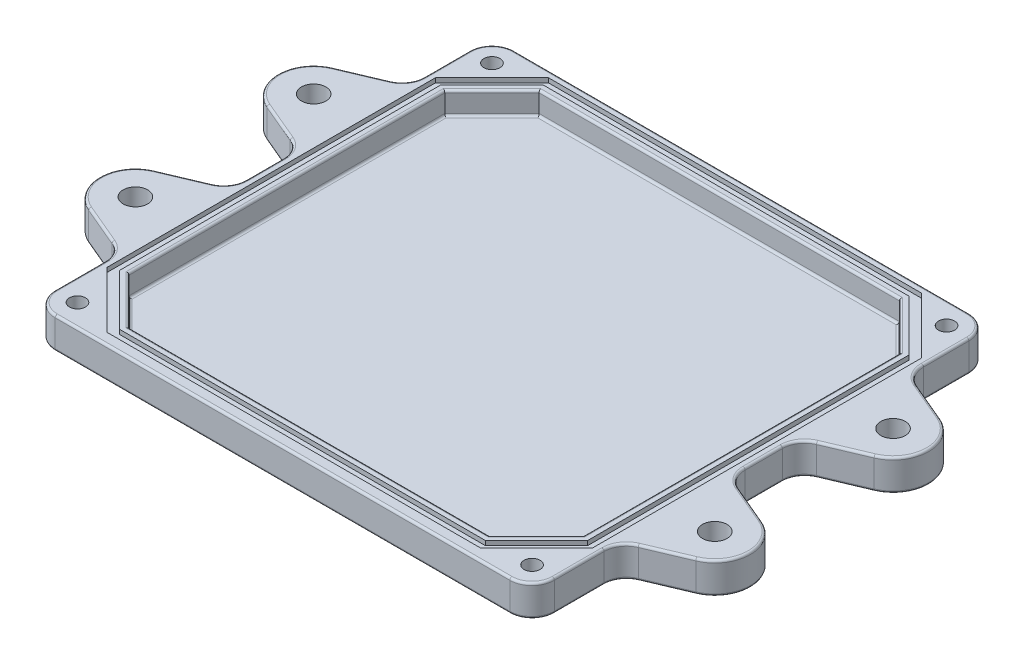
SolidWorks part; units mm, degrees
material "ABS"
ref_plane "Front Plane" through (0, 0, 0) normal (0, 0, 1) x (1, 0, 0)
ref_plane "Top Plane" through (0, 0, 0) normal (0, 1, 0) x (1, 0, 0)
ref_plane "Right Plane" through (0, 0, 0) normal (1, 0, 0) x (0, 0, -1)
ref_plane "PCB Top Plane" through (0, 10, 0) normal (0, 1, 0) x (1, 0, 0)
sketch "PCB Sketch" plane through (0, 10, 0) normal (0, 1, 0) x (1, 0, 0)
  line L0 (-50, 35) -> (-50, -35) construction
  line L1 (-50, -35) -> (-40, -45) construction
  line L2 (-40, -45) -> (40, -45) construction
  line L3 (40, -45) -> (50, -35) construction
  line L4 (50, -35) -> (50, 35) construction
  line L5 (50, 35) -> (40, 45) construction
  line L6 (40, 45) -> (-40, 45) construction
  line L7 (-40, 45) -> (-50, 35) construction
  line L8 (-29.625, -49.5) -> (29.625, -49.5) construction
  point P4 (-40, 35)
  point P9 (40, 35)
  point P10 (40, -35)
  point P11 (-40, -35)
  point P12 (0, 12)
  point P13 (0, 45)
  point P15 (50, 0)
  point P16 (0, -40)
  point P19 (0, -49.5)
  dimension "D1" = 100
  dimension "D2" = 90
  dimension "D3" = 10
  dimension "D4" = 57
  dimension "D5" = 5
  dimension "D6" = 59.25
  dimension "D7" = 9.5
ref_plane "Connector Front Plane" through (0, 0, 49.5) normal (0, 0, 1) x (1, 0, 0)
sketch "Connector Front Sketch" plane through (0, 0, 49.5) normal (0, 0, 1) x (1, 0, 0)
  line L0 (-29.605, 45.26) -> (29.605, 45.26) construction
  line L1 (29.605, 45.26) -> (29.605, 10) construction
  line L2 (29.605, 10) -> (-29.605, 10) construction
  line L3 (-29.605, 10) -> (-29.605, 45.26) construction
  line L4 (-29.625, 10) -> (29.625, 10) construction
  line L5 (-24.65, 27.63) -> (24.65, 27.63) construction
  point P6 (0, 45.26)
  point P11 (0, 27.63)
  point P12 (29.605, 27.63)
  point P14 (-24.65, 27.63)
  point P15 (24.65, 27.63)
  dimension "D1" = 35.26
  dimension "D2" = 59.21
  dimension "D3" = 49.3
sketch "Connector Right Sketch" plane through (0, 0, 0) normal (1, 0, 0) x (0, 0, -1)
  line L0 (-49.5, 10) -> (-49.5, 45.26) construction
  line L1 (-49.5, 10) -> (-49.5, 45.26) construction
  line L2 (-49.5, 45.26) -> (-34.01, 45.26) construction
  line L3 (-34.01, 45.26) -> (-34.01, 10) construction
  line L4 (-34.01, 10) -> (-49.5, 10) construction
  line L5 (-49.5, 38.755) -> (-64.11, 38.755) construction
  line L6 (-64.11, 38.755) -> (-64.11, 16.505) construction
  line L7 (-64.11, 16.505) -> (-49.5, 16.505) construction
  line L8 (-64.11, 27.63) -> (-34.01, 27.63) construction
  line L9 (-35, 10) -> (-45, 10) construction
  line L10 (-49.5, 45.26) -> (-49.5, 10) construction
  point P12 (-34.01, 27.63)
  point P15 (-64.11, 27.63)
  dimension "D1" = 15.49
  dimension "D2" = 14.61
  dimension "D3" = 22.25
sketch "Base Sketch" plane through (0, 0, 0) normal (0, 1, 0) x (1, 0, 0)
  line L0 (40, 45) -> (-40, 45) construction
  line L1 (-56, 51) -> (56, 51)
  line L2 (-56, 51) -> (-56, -52)
  line L3 (-56, -52) -> (56, -52)
  line L4 (56, 51) -> (56, -52)
  line L5 (-50, 35) -> (-50, -35) construction
  line L6 (-29.625, -49.5) -> (29.625, -49.5) construction
  point P8 (0, 51)
  dimension "D1" = 6
  dimension "D2" = 6
  dimension "D3" = 2.5
extrude "Base" add sketch "Base Sketch" along normal blind 7
fillet "Corner Fillet" radius 5 4 edges at (56, 3.5, -51) (56, 3.5, 52) (-56, 3.5, 52) (-56, 3.5, -51)
sketch "Rear Left Mounting Flange Sketch" plane through (0, 0, 0) normal (0, 1, 0) x (1, 0, 0)
  line L0 (-68.1201, 12.6335) -> (-56, 7.5)
  line L1 (-56, 46) -> (-56, -47) construction
  line L2 (-68.1201, 27.3665) -> (-56, 32.5)
  line L3 (-56, 32.5) -> (-56, 7.5)
  arc A0 (-68.1201, 27.3665) -> (-68.1201, 12.6335) centre (-65, 20) ccw
  circle A1 centre (-65, 20) radius 2.75
  dimension "D1" = 8
  dimension "D5" = 5.5
  dimension "D2" = 9
  dimension "D3" = 20
  dimension "D4" = 25
extrude "Rear Left Mounting Flange" add sketch "Rear Left Mounting Flange Sketch" along normal up to surface (7 mm away) up to face at (0, 7, 0.5)
mirror "Rear Right Mounting Flange" about plane through (0, 0, 0) normal (1, 0, 0) of "Rear Left Mounting Flange"
mirror "Front Mounting Flanges" about plane through (0, 0, 0) normal (0, 0, 1) of "Rear Right Mounting Flange", "Rear Left Mounting Flange"
fillet "Mounting Flange Fillet" radius 5 8 edges at (-56, 3.5, -32.5) (-56, 3.5, -7.5) (-56, 3.5, 7.5) (-56, 3.5, 32.5) (56, 3.5, -32.5) (56, 3.5, -7.5) (56, 3.5, 7.5) (56, 3.5, 32.5)
fillet "Top and Bottom Fillet" radius 0.5 64 edges at (-54.5355, 0, 50.5355) (-56, 0, 41.4061) (-56.8316, 0, 33.0509) (-63.585, 0, 29.2873) (-73, 0, 20) (-63.585, 0, 10.7127) (-56.8316, 0, 6.9491) (-56, 0, 0) (-56.8316, 0, -6.9491) (-63.585, 0, -10.7127) (-73, 0, -20) (-63.585, 0, -29.2873) (-56.8316, 0, -33.0509) (-56, 0, -40.9061) (-54.5355, 0, -49.5355) (0, 0, -51) (54.5355, 0, -49.5355) (56, 0, -40.9061) (56.8316, 0, -33.0509) (63.585, 0, -29.2873) (73, 0, -20) (63.585, 0, -10.7127) (56.8316, 0, -6.9491) (56, 0, 0) (56.8316, 0, 6.9491) (63.585, 0, 10.7127) (73, 0, 20) (63.585, 0, 29.2873) (56.8316, 0, 33.0509) (56, 0, 41.4061) (54.5355, 0, 50.5355) (-54.5355, 7, 50.5355) (-56, 7, 41.4061) (-56.8316, 7, 33.0509) (-63.585, 7, 29.2873) (-73, 7, 20) (-63.585, 7, 10.7127) (-56.8316, 7, 6.9491) (-56, 7, 0) (-56.8316, 7, -6.9491) (-63.585, 7, -10.7127) (-73, 7, -20) (-63.585, 7, -29.2873) (-56.8316, 7, -33.0509) (-56, 7, -40.9061) (-54.5355, 7, -49.5355) (0, 7, -51) (54.5355, 7, -49.5355) (56, 7, -40.9061) (56.8316, 7, -33.0509) (63.585, 7, -29.2873) (73, 7, -20) (63.585, 7, -10.7127) (56.8316, 7, -6.9491) (56, 7, 0) (56.8316, 7, 6.9491) (63.585, 7, 10.7127) (73, 7, 20) (63.585, 7, 29.2873) (56.8316, 7, 33.0509) (56, 7, 41.4061) (54.5355, 7, 50.5355) (0, 0, 52) (0, 7, 52)
sketch "PCB Pocket Sketch" plane through (0, 7, 0) normal (0, 1, 0) x (1, 0, 0)
  line L16 (-40.4142, 46) -> (-51, 35.4142)
  line L17 (-51, 35.4142) -> (-51, -35.4142)
  line L18 (-51, -35.4142) -> (-40.4142, -46)
  line L19 (-40.4142, -46) -> (40.4142, -46)
  line L20 (40.4142, -46) -> (51, -35.4142)
  line L21 (51, -35.4142) -> (51, 35.4142)
  line L22 (51, 35.4142) -> (40.4142, 46)
  line L23 (40.4142, 46) -> (-40.4142, 46)
  line L24 (-40.4142, 46) -> (-51, 35.4142)
  line L25 (-51, 35.4142) -> (-51, -35.4142)
  line L26 (-51, -35.4142) -> (-40.4142, -46)
  line L27 (-40.4142, -46) -> (40.4142, -46)
  line L28 (40.4142, -46) -> (51, -35.4142)
  line L29 (51, -35.4142) -> (51, 35.4142)
  line L30 (51, 35.4142) -> (40.4142, 46)
  line L31 (40.4142, 46) -> (-40.4142, 46)
  dimension "D1" = 1
extrude "PCB Pocket" cut sketch "PCB Pocket Sketch" against normal blind 5
fillet "Inside Fillet" radius 0.5 16 edges at (45.7071, 2, 40.7071) (45.7071, 7, 40.7071) (51, 2, 0) (51, 7, 0) (0, 7, 46) (0, 2, 46) (-45.7071, 2, 40.7071) (-45.7071, 7, 40.7071) (-51, 7, 0) (-45.7071, 7, -40.7071) (0, 7, -46) (45.7071, 7, -40.7071) (45.7071, 2, -40.7071) (0, 2, -46) (-51, 2, 0) (-45.7071, 2, -40.7071)
sketch "Sealing Channel Sketch" plane through (0, 7, 0) normal (0, 1, 0) x (1, 0, 0)
  line L8 (-41.864, 49.5) -> (-54.5, 36.864)
  line L9 (-54.5, 36.864) -> (-54.5, -36.864)
  line L10 (-54.5, -36.864) -> (-41.864, -49.5)
  line L11 (-41.864, -49.5) -> (41.864, -49.5)
  line L12 (41.864, -49.5) -> (54.5, -36.864)
  line L13 (54.5, -36.864) -> (54.5, 36.864)
  line L14 (54.5, 36.864) -> (41.864, 49.5)
  line L15 (41.864, 49.5) -> (-41.864, 49.5)
  line L16 (-41.0355, 47.5) -> (-52.5, 36.0355)
  line L17 (-52.5, 36.0355) -> (-52.5, -36.0355)
  line L18 (-52.5, -36.0355) -> (-41.0355, -47.5)
  line L19 (-41.0355, -47.5) -> (41.0355, -47.5)
  line L20 (41.0355, -47.5) -> (52.5, -36.0355)
  line L21 (52.5, -36.0355) -> (52.5, 36.0355)
  line L22 (52.5, 36.0355) -> (41.0355, 47.5)
  line L23 (41.0355, 47.5) -> (-41.0355, 47.5)
  line L24 (-41.0355, 47.5) -> (-52.5, 36.0355)
  line L25 (-52.5, 36.0355) -> (-52.5, -36.0355)
  line L26 (-52.5, -36.0355) -> (-41.0355, -47.5)
  line L27 (-41.0355, -47.5) -> (41.0355, -47.5)
  line L28 (41.0355, -47.5) -> (52.5, -36.0355)
  line L29 (52.5, -36.0355) -> (52.5, 36.0355)
  line L30 (52.5, 36.0355) -> (41.0355, 47.5)
  line L31 (41.0355, 47.5) -> (-41.0355, 47.5)
  dimension "D1" = 1.5
  dimension "D2" = 2
extrude "Sealing Channel" cut sketch "Sealing Channel Sketch" against normal blind 1
hole_wizard "CBORE for M3 Hex Head Machine Screw1" positions "Enclosure Mounting Hole Sketch" profile "M3 Countersunk Low Profile Hole Sketch" counterbore size "M3" standard "ANSI Metric"
sketch "Enclosure Mounting Hole Sketch" plane through (0, 0, 0) normal (0, -1, 0) x (-1, 0, 0)
  line L8 (56, 51) -> (-56, 51)
  line L9 (-56, 51) -> (-56, -52)
  line L10 (-56, -52) -> (56, -52)
  line L11 (56, -52) -> (56, 51)
  line L12 (56, 51) -> (-56, 51) construction
  line L13 (-56, 51) -> (-56, -52) construction
  line L14 (-56, -52) -> (56, -52) construction
  line L15 (56, -52) -> (56, 51) construction
  point P0 (51, -47)
  point P2 (51, 46)
  point P4 (-51, 46)
  point P6 (-51, -47)
  dimension "D2" = 5
  dimension "D3" = 5
  dimension "D4" = 5
  dimension "D5" = 5
  dimension "D1" = 0
sketch "M3 Countersunk Low Profile Hole Sketch" plane through (-51, 0, 47) normal (1, 0, 0) x (0, 0, -1)
  line L0 (0, 0) -> (0, 8.0815)
  line L1 (0, 8.0815) -> (1.8, 7)
  line L2 (1.8, 7) -> (1.8, 2)
  line L3 (1.8, 2) -> (3, 2)
  line L4 (3, 2) -> (3, 0)
  line L5 (3, 0) -> (0, 0)
  line L10 (0, 8.0815) -> (-1.8, 7) construction
  line L11 (0, -6.35) -> (0, 107.95) construction
  dimension "Hole Dia." = 3.6
  dimension "Hole Depth" = 7
  dimension "C'Bore Dia." = 6
  dimension "C'Bore Depth" = 2
  dimension "Drill Angle" = 118
ref_axis "Enclosure Rear Left Axis" through (-51, 30.7147, -46) along (0, -1, 0)
ref_axis "Enclosure Front Left Axis" through (-51, 42.5655, 47) along (0, -1, 0)
ref_axis "Enclosure Front Right Axis" through (51, 44.5272, 47) along (0, -1, 0)
ref_axis "Enclosure Rear Right Axis" through (51, 56.0968, -46) along (0, -1, 0)
ref_plane "Enclosure Bottom Plane" through (0, 7, 0) normal (0, 1, 0) x (1, 0, 0)
ref_plane "Enclosure Mounting Screw Plane" through (0, 2, 0) normal (0, -1, 0) x (-1, 0, 0)
